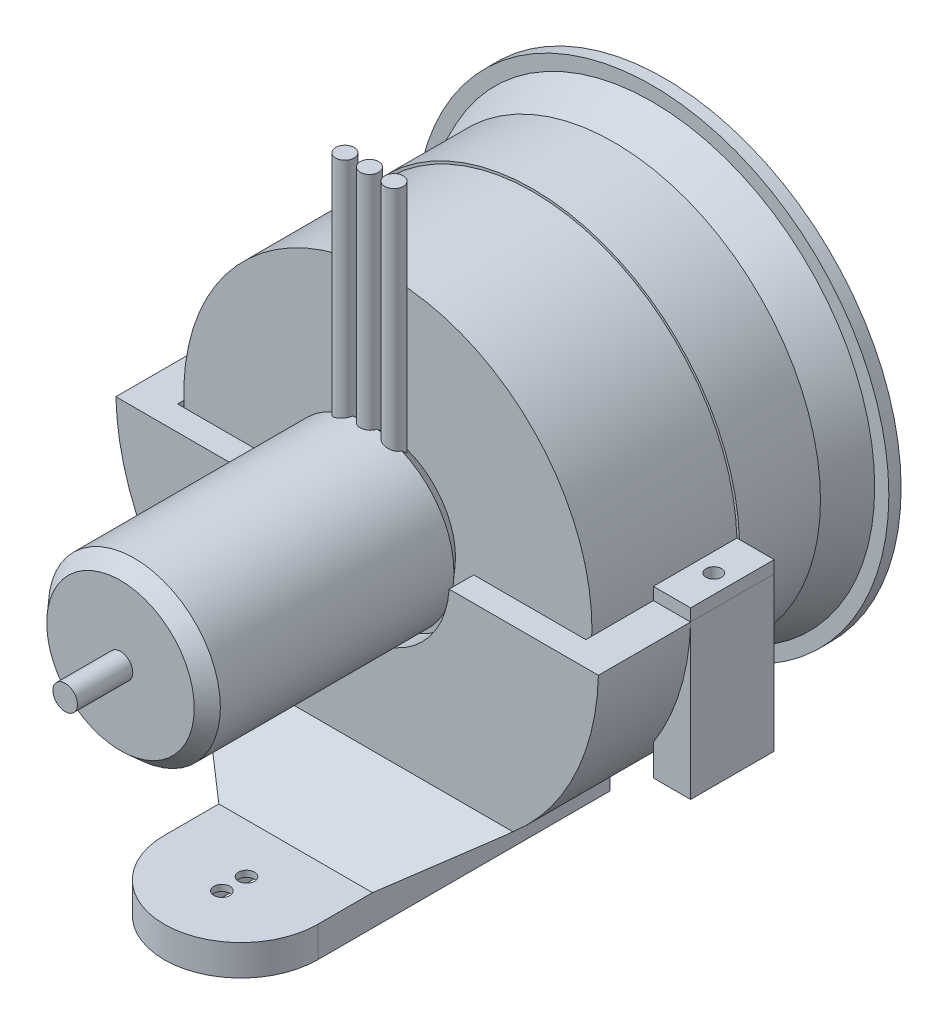
SolidWorks part; units mm, degrees
ref_plane "Front Plane" through (0, 0, 0) normal (1, 0, 0) x (0, 1, 0)
ref_plane "Top Plane" through (0, 0, 0) normal (0, 0, 1) x (0, 1, 0)
ref_plane "Right Plane" through (0, 0, 0) normal (0, 1, 0) x (-1, 0, 0)
sketch "Sketch1" plane through (0, 0, 0) normal (1, 0, 0) x (0, 1, 0)
  line L0 (0, 0) -> (0, -32.442) construction
  line L1 (0, 0) -> (38.5, 0)
  line L2 (38.5, 0) -> (38.5, 2)
  line L3 (38.5, 2) -> (36.2, 2)
  line L4 (36.2, 2) -> (33.6, 8.225)
  line L5 (33.6, 8.225) -> (33.6, 21.4)
  line L6 (33.2, 21.4) -> (33.2, 45)
  line L7 (33.2, 45) -> (5, 45)
  line L9 (5, 46) -> (12, 46)
  line L10 (12, 46) -> (14, 48.25)
  line L11 (14, 48.25) -> (14, 86.25)
  line L12 (14, 86.25) -> (12, 88.5)
  line L13 (12, 88.5) -> (2, 88.5)
  line L14 (2, 88.5) -> (2, 97.5)
  line L15 (2, 97.5) -> (0, 97.5)
  line L17 (33.2, 21.4) -> (33.6, 21.4)
  line L19 (0, 97.5) -> (0, 0)
  line L20 (5, 46) -> (5, 45)
  dimension "D1" = 77
  dimension "D2" = 72.4
  dimension "D3" = 67.2
  dimension "D4" = 66.4
  dimension "D5" = 45
  dimension "D6" = 23.6
  dimension "D7" = 97.5
  dimension "D8" = 2
  dimension "D9" = 4
  dimension "D10" = 28
  dimension "D11" = 1
  dimension "D12" = 42.5
  dimension "D13" = 10
  dimension "D14" = 10
  dimension "D15" = 38
revolve "Revolve1" add sketch "Sketch1" angle 360 about L0
sketch "Sketch3" plane through (0, 0, 0) normal (1, 0, 0) x (0, 1, 0)
  line L0 (33.2, 45) -> (-33.2, 45) construction
  line L1 (-1, 35) -> (1, 35)
  line L2 (-1, 35) -> (-1, 21.4)
  line L3 (-1, 21.4) -> (1, 21.4)
  line L4 (1, 35) -> (1, 21.4)
  point P4 (0, 21.4)
  dimension "D1" = 13.6
  dimension "D2" = 10
  dimension "D3" = 2
extrude "Boss-Extrude1" add sketch "Sketch3" along normal mid plane 78.5
sketch "Sketch4" plane through (0, 1, 0) normal (0, 1, 0) x (-1, 0, 0)
  line L0 (-39.25, 35) -> (-33.1849, 35) construction
  line L1 (-39.25, 28.2) -> (-33.1849, 28.2) construction
  line L4 (-39.25, 21.4) -> (-39.25, 35) construction
  line L5 (-33.1849, 21.4) -> (-33.1849, 35) construction
  circle A0 centre (-36.2175, 28.2) radius 1.25
  dimension "D2" = 2.5
  dimension "D1" = 6.8
extrude "Cut-Extrude1" cut sketch "Sketch4" against normal through all
mirror "Mirror1" about plane through (0, 0, 0) normal (1, 0, 0) of "Cut-Extrude1"
sketch "Sketch5" plane through (0, 0, 0) normal (0, 1, 0) x (-1, 0, 0)
  line L2 (-12, 46) -> (12, 46) construction
  circle A0 centre (0, 48) radius 1.5
  circle A1 centre (4, 48) radius 1.5
  circle A2 centre (-4, 48) radius 1.5
  dimension "D1" = 3
  dimension "D2" = 0.5
  dimension "D3" = 1
  dimension "D4" = 1
extrude "Boss-Extrude5" add sketch "Sketch5" along normal blind 50
sketch "Sketch6" plane through (0, 0, 45) normal (0, 0, 1) x (1, 0, 0)
  line L0 (39.25, -1) -> (33.1849, -1)
  line L1 (-39.25, -1) -> (-33.2049, -1)
  line L2 (-39.25, -1) -> (-39.25, -26)
  line L3 (-39.25, -26) -> (-33.2049, -26)
  line L4 (-33.2049, -26) -> (-33.2049, -20.9522)
  line L5 (39.25, -1) -> (39.25, -26)
  line L6 (39.25, -26) -> (33.1849, -26)
  line L7 (33.1849, -26) -> (33.1849, -20.9839)
  arc A0 (-33.2049, -1) -> (33.2049, -1) centre (0, 0) ccw
  arc A1 (-39.25, -1) -> (39.25, -1) centre (0, 0) ccw
  circle A2 centre (0, 0) radius 33.2 construction
  dimension "D1" = 0.02
  dimension "D2" = 25
extrude "Boss-Extrude6" add sketch "Sketch6" against normal up to surface (23.6 mm away) and the other way blind 5 separate body contours L1 A1 L0 A0 region at (36.7349, -11.149, 45) up to face at (-36.4213, 0, 21.4)
extrude "Boss-Extrude7" add sketch "Sketch6<4>" along normal up to surface (-10 mm away) from surface contours A1 L7 L6 L5 | A1 L2 L3 L4 region at (36.9268, -19.1147, 45) region at (-36.932, -19.1085, 45) up to face at (36.2212, 0, 35) starting at face at (36.4213, 0, 21.4)
sketch "Sketch6<4>" plane through (0, 0, 45) normal (0, 0, 1) x (1, 0, 0) same geometry as "Sketch6"
sketch "Sketch7" plane through (0, -26, 0) normal (0, -1, 0) x (1, 0, 0)
  circle A0 centre (-36.2175, 28.2) radius 1.25 construction
  circle A1 centre (-36.2175, 28.2) radius 1.25
extrude "Cut-Extrude2" cut sketch "Sketch7" against normal through all
mirror "Mirror2" about plane through (0, 0, 0) normal (1, 0, 0) of "Cut-Extrude2"
sketch "Sketch8" plane through (0, 0, 50) normal (0, 0, 1) x (1, 0, 0)
  line L0 (-33.2049, -1) -> (-14.9666, -1)
  line L1 (33.2049, -1) -> (14.9666, -1)
  circle A0 centre (0, 0) radius 14 construction
  circle A1 centre (0, 0) radius 14 construction
  arc A2 (-14.9666, -1) -> (14.9666, -1) centre (0, 0) ccw
  circle A3 centre (0, 0) radius 15 construction
  arc A4 (-33.2049, -1) -> (33.2049, -1) centre (0, 0) ccw construction
  arc A5 (-33.2049, -1) -> (33.2049, -1) centre (0, 0) ccw
  dimension "D1" = 1
extrude "Boss-Extrude8" add sketch "Sketch8" against normal offset from surface (4 mm away) 1 up to face at (5, 0, 45)
ref_plane "Plane1" through (0, -45, 0) normal (0, -1, 0) x (1, 0, 0)
sketch "Sketch9" plane through (0, -45, 0) normal (0, -1, 0) x (1, 0, 0)
  line L0 (-33.2049, 21.4) -> (33.1849, 21.4) construction
  line L1 (-12.5, 81.4) -> (12.5, 81.4)
  line L2 (-12.5, 81.4) -> (-12.5, 21.4)
  line L3 (-12.5, 21.4) -> (12.5, 21.4)
  line L4 (12.5, 81.4) -> (12.5, 21.4)
  line L5 (4, 61.4257) -> (4, 72) construction
  line L6 (-4, 72) -> (-4, 61.4257) construction
  line L7 (4, 61.4257) -> (4, 72) construction
  line L8 (-4, 72) -> (-4, 61.4257) construction
  line L9 (4.05, 61.4257) -> (4.05, 72)
  line L10 (-4.05, 72) -> (-4.05, 61.4257)
  arc A0 (0, 38.025) -> (0, 57.975) centre (0, 48) ccw construction
  arc A1 (4, 61.4257) -> (5.15, 54.7416) centre (24, 61.4257) ccw construction
  arc A2 (4, 72) -> (-4, 72) centre (0, 72) ccw construction
  arc A3 (-5.15, 54.7416) -> (-4, 61.4257) centre (-24, 61.4257) ccw construction
  arc A4 (0, 57.975) -> (0, 38.025) centre (0, 48) ccw construction
  arc A5 (0, 38.025) -> (4.5207, 56.8918) centre (0, 48) ccw construction
  arc A6 (4, 61.4257) -> (4.5207, 56.8918) centre (24, 61.4257) ccw construction
  arc A7 (4, 72) -> (-4, 72) centre (0, 72) ccw construction
  arc A8 (-4.5207, 56.8918) -> (-4, 61.4257) centre (-24, 61.4257) ccw construction
  arc A9 (-4.5207, 56.8918) -> (0, 38.025) centre (0, 48) ccw construction
  arc A10 (4.05, 72) -> (-4.05, 72) centre (0, 72) ccw
  arc A11 (-4.5641, 56.9258) -> (-4.05, 61.4257) centre (-24, 61.4257) ccw
  arc A12 (-4.5641, 56.9258) -> (0, 37.975) centre (0, 48) ccw
  arc A13 (0, 37.975) -> (4.5641, 56.9258) centre (0, 48) ccw
  arc A14 (4.05, 61.4257) -> (4.5641, 56.9258) centre (24, 61.4257) ccw
  point P6 (0, 21.4)
  dimension "D1" = 60
  dimension "D2" = 25
  dimension "D3" = 0.05
extrude "Boss-Extrude9" add sketch "Sketch9" against normal blind 5 separate body contours A14 L9 A10 L10 A11 A12 A13 | L4 L1 L2 L3 L9 A14 A13 A12 A11 L10 A10 region at (0, -45, 80.75) region at (0, -45, 53.7265)
extrude "Cut-Extrude3" cut sketch "Sketch9<3>" against normal blind 4 contours A14 L9 A10 L10 A11 A12 A13 region at (0, -45, 53.7265)
sketch "Sketch9<3>" plane through (0, -45, 0) normal (0, -1, 0) x (1, 0, 0) same geometry as "Sketch9"
sketch "Sketch10" plane through (0, -40, 0) normal (0, 1, 0) x (-1, 0, 0)
  line L0 (39.25, 50) -> (-39.25, 50) construction
  line L1 (-12.5, 50) -> (12.5, 50)
  line L2 (-12.5, 50) -> (-12.5, 21.4)
  line L3 (-12.5, 21.4) -> (12.5, 21.4)
  line L4 (12.5, 50) -> (12.5, 21.4)
  line L5 (-33.1849, 21.4) -> (33.2049, 21.4) construction
  line L6 (12.5, 81.4) -> (12.5, 21.4) construction
  line L7 (-12.5, 81.4) -> (-12.5, 21.4) construction
extrude "Boss-Extrude10" add sketch "Sketch10" along normal up to surface (2.7802 mm away) up to face at (-0.0055, -18.1561, 35.35)
sketch "Sketch11" plane through (0, -40, 0) normal (0, 1, 0) x (1, 0, 0)
  arc A0 (0, -69.3) -> (0, -66.7) centre (0, -68) ccw construction
  arc A1 (0, -66.7) -> (0, -69.3) centre (0, -68) ccw construction
  arc A2 (0, -73.3) -> (0, -70.7) centre (0, -72) ccw construction
  arc A3 (0, -70.7) -> (0, -73.3) centre (0, -72) ccw construction
  arc A4 (0, -69.3) -> (0, -66.7) centre (0, -68) ccw
  arc A5 (0, -66.7) -> (0, -69.3) centre (0, -68) ccw
  arc A6 (0, -73.3) -> (0, -70.7) centre (0, -72) ccw
  arc A7 (0, -70.7) -> (0, -73.3) centre (0, -72) ccw
extrude "Cut-Extrude4" cut sketch "Sketch11" against normal through all
fillet "Fillet1" 2 edges at (-12.5, -42.5, 81.4) (12.5, -42.5, 81.4) type full round first side face at (-12.5, -40.7399, 50.9333) second side face at (12.5, -40.7399, 50.9333) middle face at (0, -42.5, 81.4)
delete or keep bodies "Body-Delete/Keep 1" [suppressed] type delete bodies bodies 105
sketch "Sketch12" plane through (0, 0, 50) normal (0, 0, 1) x (1, 0, 0)
  line L0 (12.5, -40) -> (24.0746, -31.0158)
  line L1 (-12.5, -40) -> (-24.0746, -31.0158)
  line L2 (-12.5, -40) -> (-12.5, -37.2198)
  line L3 (12.5, -40) -> (12.5, -37.2198)
  arc A0 (12.5, -37.2198) -> (39.25, -1) centre (0, 0) ccw construction
  arc A1 (-39.25, -1) -> (-12.5, -37.2198) centre (0, 0) ccw construction
  arc A2 (-24.0746, -31.0158) -> (-12.5, -37.2198) centre (0, 0) ccw
  arc A3 (12.5, -37.2198) -> (24.0746, -31.0158) centre (0, 0) ccw
extrude "Boss-Extrude11" add sketch "Sketch12" against normal up to surface (28.6 mm away) up to face at (-0.0032, -25.0119, 21.4)
chamfer "Chamfer2" distance 10 angle 45 1 edges at (0, -40, 50)
